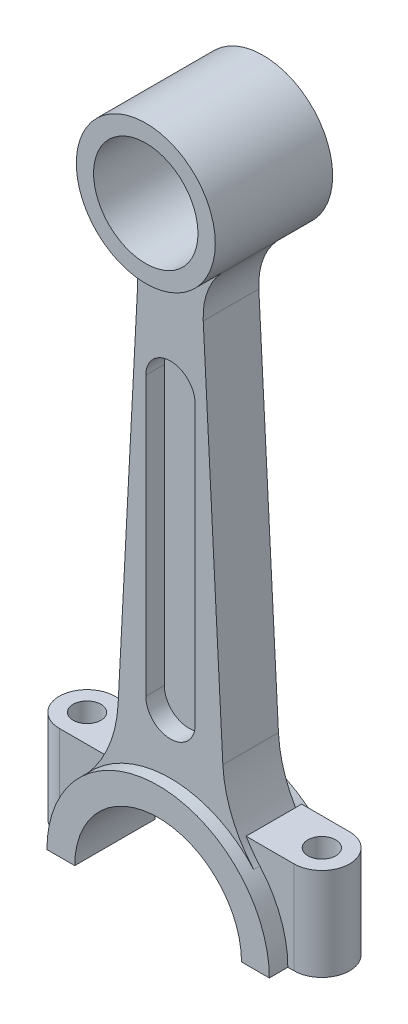
SolidWorks part; units mm, degrees
ref_plane "Front Plane" through (0, 0, 0) normal (0, 0, 1) x (1, 0, 0)
ref_plane "Top Plane" through (0, 0, 0) normal (0, 1, 0) x (1, 0, 0)
ref_plane "Right Plane" through (0, 0, 0) normal (1, 0, 0) x (0, 0, -1)
sketch "Sketch1" plane through (0, 0, 0) normal (0, 0, 1) x (1, 0, 0)
  line L0 (0, 0) -> (0, 16315.6184) construction
  line L1 (0, 0) -> (-16315.6184, 0) construction
  line L2 (-36, 0) -> (36, 0)
  line L3 (-36, 0) -> (-47, 0)
  line L4 (-47, 0) -> (-47, 30)
  line L5 (-47, 30) -> (-22.4835, 30)
  line L6 (47, 30) -> (22.4835, 30)
  line L7 (47, 0) -> (47, 30)
  line L8 (0, 145) -> (0, 55) construction
  line L9 (8, 145) -> (8, 55)
  line L10 (-8, 145) -> (-8, 55)
  line L11 (10, 181.0444) -> (16.9576, 48.2859)
  line L12 (-10, 181.0444) -> (-16.9576, 48.2859)
  line L13 (-47, 0) -> (-36, 0)
  line L14 (36, 0) -> (47, 0)
  arc A0 (36, 0) -> (-36, 0) centre (0, 0) ccw
  arc A1 (27, 0) -> (-27, 0) centre (0, 0) ccw
  circle A2 centre (0, 201.2) radius 16.9
  circle A3 centre (0, 201.2) radius 22.5
  arc A4 (8, 145) -> (-8, 145) centre (0, 145) ccw
  arc A5 (-8, 55) -> (8, 55) centre (0, 55) ccw
  arc A6 (16.9576, 48.2859) -> (26.9539, 23.8639) centre (56.9028, 50.3793) ccw
  arc A7 (-16.9576, 48.2859) -> (-26.9539, 23.8639) centre (-56.9028, 50.3793) cw
  point P21 (0, 100)
  dimension "D1" = 72
  dimension "D2" = 54
  dimension "D5" = 33.8
  dimension "D6" = 45
  dimension "D9" = 8
  dimension "D12" = 40
  dimension "D3" = 47
  dimension "D4" = 30
  dimension "D7" = 201.2
  dimension "D8" = 90
  dimension "D10" = 20
  dimension "D11" = 6
  dimension "D13" = 55
extrude "Boss-Extrude1" add sketch "Sketch1" along normal mid plane 38 contours A3 A2 region at (-11.5231, 219.7805, 0)
extrude "Boss-Extrude2" add sketch "Sketch1<3>" along normal blind 11 and the other way blind 7 from offset 0 contours A3 L12 A0 L11 A5 L10 A4 L9 region at (-24.4385, 26.7278, 0)
sketch "Sketch1<3>" plane through (0, 0, 0) normal (0, 0, 1) x (1, 0, 0) same geometry as "Sketch1"
extrude "Boss-Extrude3" add sketch "Sketch1<4>" along normal blind 15 and the other way blind 11 contours A1 L2 A0 region at (-32.9099, 12.4751, 0)
sketch "Sketch1<4>" plane through (0, 0, 0) normal (0, 0, 1) x (1, 0, 0) same geometry as "Sketch1"
extrude "Boss-Extrude4" add sketch "Sketch1<6>" along normal mid plane 18 contours A0 L5 L4 L3 | A0 L14 L7 L6 region at (-38.6271, 17.2616, 0) region at (38.6271, 17.2616, 0)
sketch "Sketch1<6>" plane through (0, 0, 0) normal (0, 0, 1) x (1, 0, 0) same geometry as "Sketch1"
fillet "Fillet1" 2 edges at (47, 15, -9) (47, 15, 9) type full round first side face at (36.2954, 16.9172, -9) second side face at (36.2954, 16.9172, 9) middle face at (47, 15, 0)
fillet "Fillet2" 2 edges at (-47, 15, 9) (-47, 15, -9) type full round first side face at (-36.2954, 16.9172, 9) second side face at (-36.2954, 16.9172, -9) middle face at (-47, 15, 0)
sketch "Sketch2" plane through (0, 30, 0) normal (0, 1, 0) x (1, 0, 0)
  circle A0 centre (38, 0) radius 4.5
  circle A1 centre (-38, 0) radius 4.5
  arc A3 (38, -9) -> (38, 9) centre (38, 0) ccw construction
  dimension "D1" = 9
  dimension "D2" = 9
extrude "Cut-Extrude1" cut sketch "Sketch2" against normal blind 78
fillet "Fillet5" radius 22.5 2 edges at (10, 181.0444, 2) (-10, 181.0444, 2)
extrude "Boss-Extrude5" add sketch "Sketch1<7>" along normal mid plane 10 contours L10 A5 L9 A4 region at (0, 100, 0)
sketch "Sketch1<7>" plane through (0, 0, 0) normal (0, 0, 1) x (1, 0, 0) same geometry as "Sketch1"
